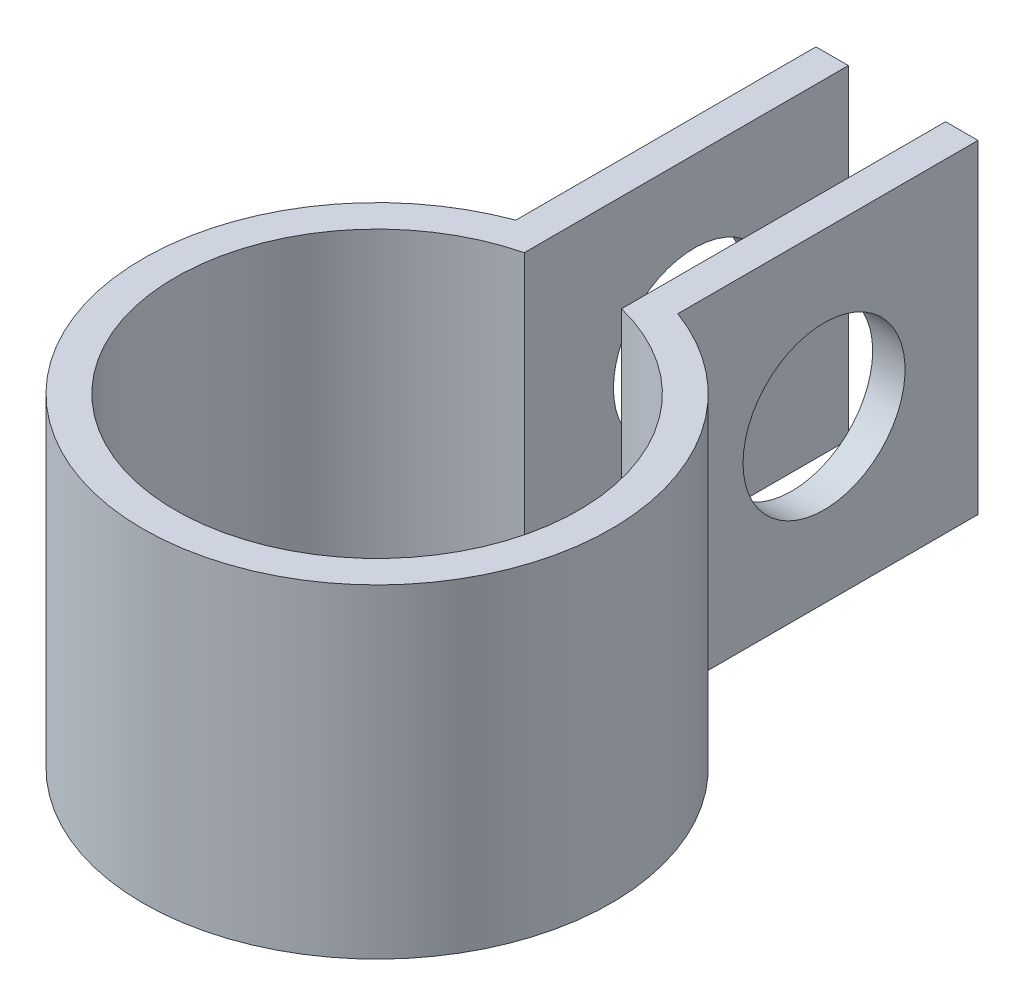
SolidWorks part; units mm, degrees
ref_plane "Front Plane" through (0, 0, 0) normal (0, 0, 1) x (1, 0, 0)
ref_plane "Top Plane" through (0, 0, 0) normal (0, 1, 0) x (1, 0, 0)
ref_plane "Right Plane" through (0, 0, 0) normal (1, 0, 0) x (0, 0, -1)
sketch "Sketch1" plane through (0, 0, 0) normal (0, 1, 0) x (1, 0, 0)
  line L0 (-1.27, 3.4436) -> (-1.27, 8.1491)
  line L1 (-1.27, 8.1491) -> (-0.762, 8.1491)
  line L3 (0, 0) -> (0, 5.6768) construction
  line L5 (1.27, 8.1491) -> (0.762, 8.1491)
  line L6 (1.27, 3.4436) -> (1.27, 8.1491)
  line L7 (-0.762, 8.1491) -> (-0.762, 3.0691)
  line L8 (0.762, 8.1491) -> (0.762, 3.0691)
  arc A0 (-0.762, 3.0691) -> (0.762, 3.0691) centre (0, 0) ccw
  arc A1 (-1.27, 3.4436) -> (1.27, 3.4436) centre (0, 0) ccw
  circle A2 centre (0, 0) radius 3.6703 construction
  circle A4 centre (0, 0) radius 3.1623 construction
  point P1 (-0.762, 3.3609)
  point P14 (-0.762, 3.4727)
  dimension "D1" = 6.3246
  dimension "D5" = 0.762
  dimension "D3" = 5.08
  dimension "D4" = 0.508
  dimension "D2" = 0.508
extrude "Boss-Extrude1" add sketch "Sketch1" along normal blind 5.08
sketch "Sketch2" plane through (-1.27, 0, 0) normal (-1, 0, 0) x (0, 0, 1)
  line L0 (-8.1491, 5.08) -> (-3.4436, 5.08) construction
  line L1 (-8.1491, 5.08) -> (-8.1491, 0) construction
  circle A0 centre (-5.7361, 2.54) radius 1.27
  point P2 (0, 0)
  dimension "D1" = 2.54
  dimension "D2" = 2.54
  dimension "D3" = 2.413
extrude "Cut-Extrude1" cut sketch "Sketch2" against normal through all
